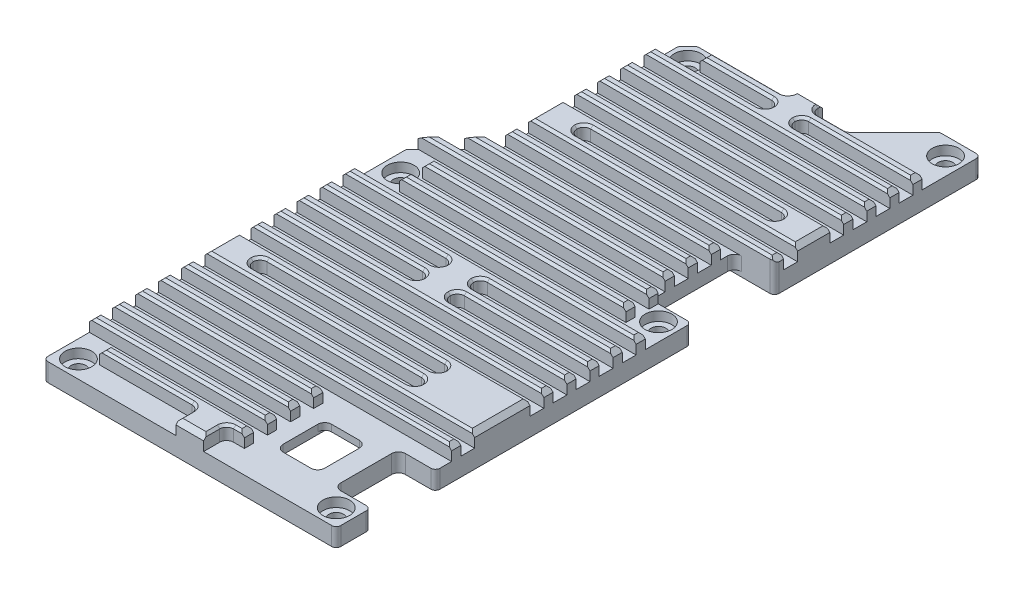
SolidWorks part; units mm, degrees
ref_plane "Front Plane" through (0, 0, 0) normal (0, 0, 1) x (1, 0, 0)
ref_plane "Top Plane" through (0, 0, 0) normal (0, 1, 0) x (1, 0, 0)
ref_plane "Right Plane" through (0, 0, 0) normal (1, 0, 0) x (0, 0, -1)
sketch "Sketch1" plane through (0, 0, 0) normal (0, 1, 0) x (1, 0, 0)
  line L2 (0, 1) -> (0, 78.3258)
  line L15 (63.5, 138.7) -> (63.5, 96)
  line L19 (10.16, 89.5213) -> (10.16, 127.0958)
  line L24 (0.2929, 79.0329) -> (9.7207, 88.4607)
  line L25 (10.4529, 127.8029) -> (11.8971, 129.2471)
  line L26 (1, 0) -> (62.5, 0)
  line L27 (12.6042, 129.54) -> (43.8287, 129.54)
  line L28 (62.5, 139.7) -> (55.0242, 139.7)
  line L29 (54.3171, 139.4071) -> (44.8893, 129.9793)
  line L30 (63.5, 76) -> (63.5, 22.5)
  line L31 (56.3, 95) -> (62.5, 95)
  line L32 (54.8, 93.5) -> (54.8, 78.5)
  line L33 (56.3, 77) -> (62.5, 77)
  line L35 (63.5, 6.5) -> (63.5, 1)
  line L36 (57, 21.5) -> (62.5, 21.5)
  line L37 (55.5, 20) -> (55.5, 9)
  line L38 (57, 7.5) -> (62.5, 7.5)
  arc A0 (63.5, 138.7) -> (62.5, 139.7) centre (62.5, 138.7) ccw
  arc A1 (54.3171, 139.4071) -> (55.0242, 139.7) centre (55.0242, 138.7) cw
  arc A2 (11.8971, 129.2471) -> (12.6042, 129.54) centre (12.6042, 128.54) cw
  arc A3 (10.4529, 127.8029) -> (10.16, 127.0958) centre (11.16, 127.0958) ccw
  arc A4 (0, 78.3258) -> (0.2929, 79.0329) centre (1, 78.3258) cw
  arc A5 (62.5, 0) -> (63.5, 1) centre (62.5, 1) ccw
  arc A6 (1, 0) -> (0, 1) centre (1, 1) cw
  arc A7 (43.8287, 129.54) -> (44.8893, 129.9793) centre (43.8287, 131.04) ccw
  arc A8 (9.7207, 88.4607) -> (10.16, 89.5213) centre (8.66, 89.5213) ccw
  arc A9 (54.8, 78.5) -> (56.3, 77) centre (56.3, 78.5) ccw
  arc A10 (56.3, 95) -> (54.8, 93.5) centre (56.3, 93.5) ccw
  arc A11 (62.5, 77) -> (63.5, 76) centre (62.5, 76) cw
  arc A12 (62.5, 95) -> (63.5, 96) centre (62.5, 96) ccw
  arc A13 (62.5, 7.5) -> (63.5, 6.5) centre (62.5, 6.5) cw
  arc A14 (62.5, 21.5) -> (63.5, 22.5) centre (62.5, 22.5) ccw
  arc A15 (55.5, 9) -> (57, 7.5) centre (57, 9) ccw
  arc A16 (57, 21.5) -> (55.5, 20) centre (57, 20) ccw
  point P15 (12.19, 129.54)
  point P20 (0, 78.74)
  point P27 (44.45, 129.54)
  point P40 (63.5, 77)
  point P49 (63.5, 7.5)
  dimension "D6" = 12.19
  dimension "D7" = 135
  dimension "D8" = 19.05
  dimension "D9" = 135
  dimension "D10" = 135
  dimension "D4" = 78.74
  dimension "D5" = 10.16
  dimension "D18" = 1
  dimension "D19" = 1
  dimension "D12" = 1
  dimension "D13" = 1.5
  dimension "D17" = 1.5
  dimension "D20" = 1.5
  dimension "D2" = 10.16
  dimension "D3" = 63.5
  dimension "D11" = 139.7
  dimension "D14" = 8.7
  dimension "D15" = 18
  dimension "D16" = 77
  dimension "D21" = 8
  dimension "D22" = 14
  dimension "D23" = 7.5
extrude "Boss-Extrude1" add sketch "Sketch1" along normal blind 6.95
sketch "Sketch2" plane through (0, 0, 0) normal (0, 1, 0) x (1, 0, 0)
  line L514 (62.5, 95) -> (46.76, 95)
  line L515 (56.3, 95) -> (62.5, 95) construction
  line L516 (45.26, 96.5) -> (45.26, 107.75)
  line L517 (43.76, 109.25) -> (39.26, 109.25)
  line L518 (37.76, 107.75) -> (37.76, 94)
  line L519 (62.5, 95) -> (62.5, 77)
  line L520 (34.76, 91) -> (34.76, 71.5)
  line L521 (36.26, 70) -> (53.76, 70)
  line L522 (55.26, 71.5) -> (55.26, 75.5)
  line L523 (62.5, 77) -> (56.76, 77)
  line L524 (63.5, 22.5) -> (63.5, 76) construction
  line L525 (34.76, 91) -> (36.26, 91) construction
  line L526 (36.26, 91) -> (36.26, 92.5) construction
  line L527 (36.26, 92.5) -> (36.26, 94) construction
  line L528 (36.26, 94) -> (37.76, 94) construction
  line L529 (19.51, 122.65) -> (56.01, 122.65)
  line L530 (57.51, 121.15) -> (57.51, 109.65)
  line L531 (56.01, 108.15) -> (49.51, 108.15)
  line L532 (48.01, 109.65) -> (48.01, 111.4)
  line L533 (46.26, 113.15) -> (33.01, 113.15)
  line L534 (31.51, 111.65) -> (31.51, 99.65)
  line L535 (30.01, 98.15) -> (19.51, 98.15)
  line L536 (18.01, 99.65) -> (18.01, 121.15)
  line L1015 (23.76, 42.1) -> (28.76, 42.1)
  line L1016 (21.76, 40.1) -> (21.76, 29.35)
  line L1017 (23.76, 27.35) -> (28.76, 27.35)
  line L1018 (30.76, 40.1) -> (30.76, 29.35)
  arc A13 (62.5, 95) -> (63.5, 96) centre (62.5, 96) ccw construction
  arc A14 (36.26, 92.5) -> (34.76, 91) centre (36.26, 91) ccw
  arc A15 (36.26, 92.5) -> (37.76, 94) centre (36.26, 94) ccw
  arc A16 (34.76, 71.5) -> (36.26, 70) centre (36.26, 71.5) ccw
  arc A17 (53.76, 70) -> (55.26, 71.5) centre (53.76, 71.5) ccw
  arc A18 (55.26, 75.5) -> (56.76, 77) centre (56.76, 75.5) cw
  arc A19 (46.76, 95) -> (45.26, 96.5) centre (46.76, 96.5) cw
  arc A20 (45.26, 107.75) -> (43.76, 109.25) centre (43.76, 107.75) ccw
  arc A21 (39.26, 109.25) -> (37.76, 107.75) centre (39.26, 107.75) ccw
  arc A22 (31.51, 99.65) -> (30.01, 98.15) centre (30.01, 99.65) cw
  arc A23 (19.51, 98.15) -> (18.01, 99.65) centre (19.51, 99.65) cw
  arc A24 (19.51, 122.65) -> (18.01, 121.15) centre (19.51, 121.15) ccw
  arc A25 (56.01, 122.65) -> (57.51, 121.15) centre (56.01, 121.15) cw
  arc A26 (57.51, 109.65) -> (56.01, 108.15) centre (56.01, 109.65) cw
  arc A27 (49.51, 108.15) -> (48.01, 109.65) centre (49.51, 109.65) cw
  arc A29 (33.01, 113.15) -> (31.51, 111.65) centre (33.01, 111.65) ccw
  arc A49 (46.26, 113.15) -> (48.01, 111.4) centre (46.26, 111.4) cw
  arc A63 (28.76, 27.35) -> (30.76, 29.35) centre (28.76, 29.35) ccw
  arc A64 (23.76, 27.35) -> (21.76, 29.35) centre (23.76, 29.35) cw
  arc A65 (28.76, 42.1) -> (30.76, 40.1) centre (28.76, 40.1) cw
  arc A66 (23.76, 42.1) -> (21.76, 40.1) centre (23.76, 40.1) ccw
  point P603 (26.26, 27.35)
  dimension "D15" = 1.5
  dimension "D26" = 1.5
  dimension "D50" = 1.75
  dimension "D51" = 1.5
  dimension "D10" = 2
  dimension "D2" = 28.74
  dimension "D3" = 14.75
  dimension "D4" = 18.24
  dimension "D6" = 7.5
  dimension "D7" = 9
  dimension "D8" = 39.25
  dimension "D9" = 7
  dimension "D11" = 27.9
  dimension "D12" = 22.5
  dimension "D13" = 4
  dimension "D14" = 20.5
  dimension "D16" = 39.5
  dimension "D17" = 13.5
  dimension "D18" = 9.5
  dimension "D19" = 9.5
  dimension "D20" = 14.5
  dimension "D21" = 24.5
  dimension "D23" = 3.9
  dimension "D25" = 2.75
sketch "Sketch11" plane through (0, 0, 0) normal (0, 1, 0) x (1, 0, 0)
  line L0 (31.2328, 67.2228) -> (31.76, 67.75) construction
  line L1 (31.76, 68.4956) -> (31.76, 67.75) construction
  line L11 (3.01, 47.7456) -> (3.01, 47) construction
  line L12 (3.5372, 46.4728) -> (3.01, 47) construction
  line L13 (27.7328, 52.2228) -> (28.26, 52.75) construction
  line L14 (28.26, 53.4956) -> (28.26, 52.75) construction
  line L23 (18.76, 92.25) -> (30.26, 92.25)
  line L24 (31.76, 90.75) -> (31.76, 68.4956)
  line L25 (31.2328, 67.2228) -> (28.7872, 64.7772)
  line L26 (28.26, 63.5044) -> (28.26, 53.4956)
  line L27 (27.7328, 52.2228) -> (20.5372, 45.0272)
  line L28 (20.01, 43.7544) -> (20.01, 26)
  line L29 (21.51, 24.5) -> (49.76, 24.5)
  line L30 (51.26, 23) -> (51.26, 6)
  line L31 (49.76, 4.5) -> (43.26, 4.5)
  line L32 (41.76, 6) -> (41.76, 6.74)
  line L33 (41, 7.5) -> (19.5056, 7.5)
  line L34 (18.2328, 8.0272) -> (9.7872, 16.4728)
  line L35 (9.26, 17.7456) -> (9.26, 40.0044)
  line L36 (8.7328, 41.2772) -> (3.5372, 46.4728)
  line L37 (3.01, 47.7456) -> (3.01, 67.5)
  line L38 (4.51, 69) -> (15.76, 69)
  line L39 (17.26, 70.5) -> (17.26, 90.75)
  line L40 (9.26, 17.7456) -> (9.26, 17) construction
  line L41 (9.7872, 16.4728) -> (9.26, 17) construction
  line L42 (1, 0) -> (62.5, 0) construction
  line L43 (63.5, 1) -> (63.5, 6.5) construction
  arc A15 (43.26, 4.5) -> (41.76, 6) centre (43.26, 6) cw
  arc A16 (51.26, 6) -> (49.76, 4.5) centre (49.76, 6) cw
  arc A17 (49.76, 24.5) -> (51.26, 23) centre (49.76, 23) cw
  arc A18 (20.01, 26) -> (21.51, 24.5) centre (21.51, 26) ccw
  arc A19 (30.26, 92.25) -> (31.76, 90.75) centre (30.26, 90.75) cw
  arc A20 (18.76, 92.25) -> (17.26, 90.75) centre (18.76, 90.75) ccw
  arc A21 (15.76, 69) -> (17.26, 70.5) centre (15.76, 70.5) ccw
  arc A22 (3.01, 67.5) -> (4.51, 69) centre (4.51, 67.5) cw
  arc A23 (19.5056, 7.5) -> (18.2328, 8.0272) centre (19.5056, 9.3) cw
  arc A24 (9.7872, 16.4728) -> (9.26, 17.7456) centre (11.06, 17.7456) cw
  arc A25 (31.76, 68.4956) -> (31.2328, 67.2228) centre (29.96, 68.4956) cw
  arc A26 (28.7872, 64.7772) -> (28.26, 63.5044) centre (30.06, 63.5044) ccw
  arc A27 (28.26, 53.4956) -> (27.7328, 52.2228) centre (26.46, 53.4956) cw
  arc A28 (20.5372, 45.0272) -> (20.01, 43.7544) centre (21.81, 43.7544) ccw
  arc A29 (9.26, 40.0044) -> (8.7328, 41.2772) centre (7.46, 40.0044) ccw
  arc A30 (3.5372, 46.4728) -> (3.01, 47.7456) centre (4.81, 47.7456) cw
  arc A31 (41.76, 6.74) -> (41, 7.5) centre (41, 6.74) ccw
  dimension "D6" = 16.25
  dimension "D30" = 1.5
  dimension "D31" = 1.8
  dimension "D32" = 0.76
  dimension "D4" = 24.5
  dimension "D5" = 22
  dimension "D7" = 7.5
  dimension "D8" = 9.26
  dimension "D16" = 14.5
  dimension "D17" = 23.25
  dimension "D19" = 14.25
  dimension "D21" = 135
  dimension "D22" = 3.5
  dimension "D23" = 6.25
  dimension "D24" = 10.75
  dimension "D25" = 17
  dimension "D26" = 67.75
  dimension "D27" = 42
  dimension "D28" = 20
  dimension "D29" = 9.5
  dimension "D35" = 52
extrude "Cut-Extrude4" cut sketch "Sketch2" along normal blind 1 contours L533 A49 L532 A27 L531 A26 L530 A25 L529 A24 L536 A23 L535 A22 L534 A29 | L517 A21 L518 A15 A14 L520 A16 L521 A17 L522 A18 L523 L519 L514 A19 L516 A20 | A66 L1015 A65 L1018 A63 L1017 A64 L1016
extrude "Cut-Extrude5" cut sketch "Sketch11" along normal blind 2
sketch "Sketch12" plane through (0, 0, 0) normal (0, -1, 0) x (1, 0, 0)
  line L0 (62.5, -77) -> (56.3, -77) construction
  line L1 (54.8, -42.1) -> (34.55, -42.1)
  line L2 (56.8, -40.1) -> (56.8, -29.35)
  line L3 (54.8, -27.35) -> (34.55, -27.35)
  line L4 (32.55, -40.1) -> (32.55, -29.35)
  line L5 (54.8, -78.5) -> (54.8, -93.5) construction
  arc A0 (54.8, -42.1) -> (56.8, -40.1) centre (54.8, -40.1) ccw
  arc A1 (56.8, -29.35) -> (54.8, -27.35) centre (54.8, -29.35) ccw
  arc A2 (34.55, -27.35) -> (32.55, -29.35) centre (34.55, -29.35) ccw
  arc A3 (34.55, -42.1) -> (32.55, -40.1) centre (34.55, -40.1) cw
  dimension "D5" = 2
  dimension "D1" = 14.75
  dimension "D2" = 24.25
  dimension "D3" = 34.9
  dimension "D4" = 2
extrude "Cut-Extrude6" cut sketch "Sketch12" against normal blind 1.2
sketch "Sketch13" plane through (0, 0, 0) normal (0, -1, 0) x (1, 0, 0)
  line L0 (36.8, -67) -> (55.3, -67)
  line L1 (56.8, -65.5) -> (56.8, -46.5)
  line L2 (55.3, -45) -> (34.05, -45)
  line L3 (32.55, -46.5) -> (32.55, -50)
  line L4 (34.05, -51.5) -> (34.5, -51.5)
  line L5 (35.3, -52.3) -> (35.3, -65.5)
  line L6 (62.5, -77) -> (56.3, -77) construction
  line L7 (54.8, -78.5) -> (54.8, -93.5) construction
  arc A0 (32.55, -50) -> (34.05, -51.5) centre (34.05, -50) ccw
  arc A1 (34.05, -45) -> (32.55, -46.5) centre (34.05, -46.5) ccw
  arc A2 (36.8, -67) -> (35.3, -65.5) centre (36.8, -65.5) cw
  arc A3 (56.8, -46.5) -> (55.3, -45) centre (55.3, -46.5) ccw
  arc A4 (55.3, -67) -> (56.8, -65.5) centre (55.3, -65.5) ccw
  arc A5 (34.5, -51.5) -> (35.3, -52.3) centre (34.5, -52.3) cw
  dimension "D7" = 1.5
  dimension "D8" = 0.8
  dimension "D1" = 24.25
  dimension "D2" = 22
  dimension "D3" = 21.5
  dimension "D4" = 6.5
  dimension "D5" = 10
  dimension "D6" = 2
extrude "Cut-Extrude7" cut sketch "Sketch13" against normal blind 2
sketch "Sketch14" plane through (0, 6.95, 0) normal (0, 1, 0) x (1, 0, 0)
  line L1 (43.5, 19) -> (49.5, 19)
  line L2 (42, 17.5) -> (42, 10)
  line L3 (43.5, 8.5) -> (49.5, 8.5)
  line L4 (51, 17.5) -> (51, 10)
  line L5 (57, 21.5) -> (62.5, 21.5) construction
  line L6 (63.5, 22.5) -> (63.5, 76) construction
  arc A0 (49.5, 8.5) -> (51, 10) centre (49.5, 10) ccw
  arc A1 (42, 10) -> (43.5, 8.5) centre (43.5, 10) ccw
  arc A2 (49.5, 19) -> (51, 17.5) centre (49.5, 17.5) cw
  arc A3 (43.5, 19) -> (42, 17.5) centre (43.5, 17.5) ccw
  dimension "D5" = 1.5
  dimension "D1" = 9
  dimension "D2" = 10.5
  dimension "D3" = 12.5
  dimension "D4" = 2.5
extrude "Cut-Extrude8" cut sketch "Sketch14" against normal through all
sketch "Sketch15" plane through (0, 6.95, 0) normal (0, 1, 0) x (1, 0, 0)
  line L0 (0, 78.3258) -> (0, 1) construction
  line L1 (0, 5) -> (63.5, 5)
  line L2 (0, 5) -> (0, 2)
  line L3 (0, 2) -> (63.5, 2)
  line L4 (63.5, 5) -> (63.5, 2)
  line L5 (63.5, 1) -> (63.5, 6.5) construction
  line L6 (1, 0) -> (62.5, 0) construction
  dimension "D1" = 2
  dimension "D2" = 3
extrude "Cut-Extrude9" cut sketch "Sketch15" against normal blind 3
pattern_linear "LPattern1" count 28 spacing 5 along (0, 0, -1) of "Cut-Extrude9"
sketch "Sketch16" plane through (0, 6.95, 0) normal (0, 1, 0) x (1, 0, 0)
  line L0 (63.5, 2) -> (63.5, 5) construction
  line L2 (38.6, 22) -> (38.6, 2)
  line L4 (63.5, 20) -> (63.5, 0)
  line L7 (43.8287, 129.54) -> (12.6042, 129.54) construction
  line L8 (43.8287, 129.54) -> (63.5, 129.54)
  line L9 (43.8287, 129.54) -> (43.8287, 139.7)
  line L10 (43.8287, 139.7) -> (63.5, 139.7)
  line L11 (63.5, 129.54) -> (63.5, 139.7)
  line L12 (63.5, 132) -> (63.5, 135) construction
  line L13 (62.5, 139.7) -> (55.0242, 139.7) construction
  line L14 (0, 2) -> (63.5, 2) construction
  line L15 (0, 10) -> (7.2, 10)
  line L16 (0, 10) -> (0, 0)
  line L18 (7.2, 10) -> (7.2, 2)
  line L21 (7.2, 2) -> (38.6, 2)
  line L23 (42, 10) -> (0, 10) construction
  line L24 (0, 0) -> (63.5, 0)
  line L25 (0, 10) -> (0, 7) construction
  line L26 (1, 0) -> (62.5, 0) construction
  line L27 (62.5, 77) -> (0, 77) construction
  line L28 (56.3, 77) -> (63.5, 77)
  line L29 (56.3, 77) -> (56.3, 70)
  line L30 (56.3, 70) -> (63.5, 70)
  line L31 (63.5, 77) -> (63.5, 70)
  line L32 (63.5, 70) -> (0, 70) construction
  line L33 (63.5, 67) -> (63.5, 70) construction
  line L34 (63.5, 70) -> (0, 70) construction
  line L35 (0, 77) -> (7.2, 77)
  line L36 (0, 77) -> (0, 70)
  line L37 (0, 70) -> (7.2, 70)
  line L38 (7.2, 77) -> (7.2, 70)
  line L39 (0, 22) -> (63.366, 22) construction
  line L40 (10.16, 122) -> (17.36, 122)
  line L41 (10.16, 122) -> (10.16, 129.54)
  line L42 (10.16, 129.54) -> (17.36, 129.54)
  line L43 (17.36, 122) -> (17.36, 129.54)
  line L46 (38.6, 22) -> (63.5, 22)
  line L47 (63.5, 20) -> (63.5, 22)
  line L49 (0, 22) -> (63.366, 22) construction
  dimension "D1" = 24.9
  dimension "D2" = 7.2
  dimension "D3" = 7.2
  dimension "D4" = 7.2
  dimension "D5" = 7.2
extrude "Cut-Extrude10" cut sketch "Sketch16" against normal blind 3
hole_wizard "Ø3.2 (3.2) Diameter Hole1" positions "Sketch18" profile "Sketch17" hole size "Ø3.2" standard "ISO" end condition up to next
sketch "Sketch18" plane through (0, 3.95, 0) normal (0, 1, 0) x (1, 0, 0)
  line L0 (1, 0) -> (62.5, 0) construction
  line L1 (63.5, 1) -> (63.5, 6.5) construction
  line L2 (0, 10) -> (0, 1) construction
  line L3 (63.5, 67) -> (63.5, 76) construction
  line L4 (0, 78.3258) -> (0, 67) construction
  line L5 (10.16, 127.0958) -> (10.16, 122) construction
  line L6 (43.8287, 129.54) -> (12.6042, 129.54) construction
  line L7 (63.5, 127) -> (63.5, 138.7) construction
  line L8 (62.5, 139.7) -> (55.0242, 139.7) construction
  point P0 (59.69, 3.81)
  point P1 (3.81, 3.81)
  point P3 (3.81, 73.66)
  point P5 (59.69, 73.66)
  point P7 (13.97, 125.73)
  point P9 (59.69, 135.89)
  dimension "D1" = 3.81
  dimension "D2" = 3.81
  dimension "D3" = 3.81
  dimension "D4" = 3.81
  dimension "D5" = 3.81
  dimension "D6" = 3.81
  dimension "D7" = 3.81
  dimension "D8" = 3.81
  dimension "D9" = 3.81
  dimension "D10" = 3.81
  dimension "D11" = 69.85
  dimension "D12" = 69.85
sketch "Sketch17" plane through (59.69, 3.95, -3.81) normal (1, 0, 0) x (0, 0, 1)
  line L0 (0, 0) -> (0, 3.95)
  line L1 (0, 3.95) -> (1.6, 3.95)
  line L2 (1.6, 3.95) -> (1.6, 0)
  line L5 (1.6, 0) -> (0, 0)
  line L11 (0, -6.35) -> (0, 107.95) construction
  dimension "Thru Hole Dia." = 3.2
  dimension "Thru Hole Depth" = 3.95
sketch "Sketch19" plane through (0, 3.95, 0) normal (0, 1, 0) x (1, 0, 0)
  circle A0 centre (3.81, 3.81) radius 2.9
  circle A1 centre (59.69, 3.81) radius 2.9
  circle A2 centre (3.81, 73.66) radius 2.9
  circle A3 centre (59.69, 73.66) radius 2.9
  circle A4 centre (13.97, 125.73) radius 2.9
  circle A5 centre (59.69, 135.89) radius 2.9
  dimension "D1" = 5.8
  dimension "D2" = 5.8
  dimension "D3" = 5.8
  dimension "D4" = 5.8
  dimension "D5" = 5.8
  dimension "D6" = 5.8
extrude "Cut-Extrude11" cut sketch "Sketch19" against normal blind 2
sketch "Sketch20" plane through (0, 3.95, 0) normal (0, 1, 0) x (1, 0, 0)
  line L0 (1, 0) -> (62.5, 0) construction
  line L1 (28.75, 0) -> (34.75, 0)
  line L2 (28.75, 0) -> (28.75, 7)
  line L3 (28.75, 7) -> (34.75, 7)
  line L4 (34.75, 0) -> (34.75, 7)
  line L5 (63.5, 30) -> (0, 30) construction
  line L7 (43.8287, 129.54) -> (12.6042, 129.54) construction
  line L8 (34.41, 129.54) -> (39.41, 129.54)
  line L9 (34.41, 129.54) -> (34.41, 122)
  line L10 (34.41, 122) -> (39.41, 122)
  line L11 (39.41, 129.54) -> (39.41, 122)
  line L12 (63.5, 35) -> (0, 35) construction
  line L13 (10.16, 127.0958) -> (10.16, 122) construction
  line L14 (10.16, 122) -> (63.5, 122) construction
  line L15 (0, 42) -> (7, 42)
  line L16 (0, 42) -> (0, 35)
  line L17 (0, 35) -> (7, 35)
  line L18 (7, 42) -> (7, 35)
  line L19 (31.75, 7) -> (31.75, 0) construction
  line L20 (63.5, 42) -> (48.5, 42)
  line L21 (63.5, 42) -> (63.5, 30)
  line L22 (63.5, 30) -> (48.5, 30)
  line L23 (48.5, 42) -> (48.5, 30)
  line L24 (0, 10) -> (0, 1) construction
  line L25 (28.75, 60) -> (34.75, 60)
  line L26 (28.75, 60) -> (28.75, 52)
  line L27 (28.75, 52) -> (34.75, 52)
  line L28 (34.75, 60) -> (34.75, 52)
  line L30 (0, 55) -> (0, 52) construction
  line L35 (63.5, 60) -> (0, 60) construction
  line L36 (0, 52) -> (63.5, 52) construction
  line L37 (10.16, 95) -> (62.5, 95) construction
  line L38 (10.16, 102) -> (17.16, 102)
  line L39 (10.16, 102) -> (10.16, 95)
  line L40 (10.16, 95) -> (17.16, 95)
  line L41 (17.16, 102) -> (17.16, 95)
  line L42 (63.5, 100) -> (10.16, 100) construction
  line L43 (56.5, 100) -> (63.5, 100)
  line L44 (56.5, 100) -> (56.5, 107)
  line L45 (56.5, 107) -> (63.5, 107)
  line L46 (63.5, 100) -> (63.5, 107)
  line L47 (7.2, 7) -> (38.6, 7) construction
  point P20 (34.41, 125.77)
  point P47 (28.75, 56)
  point P60 (63.5, 103.5)
  dimension "D2" = 6
  dimension "D3" = 5
  dimension "D4" = 24.25
  dimension "D5" = 7
  dimension "D6" = 15
  dimension "D7" = 6
  dimension "D8" = 28.75
  dimension "D9" = 7
  dimension "D10" = 7
  dimension "D11" = 31.75
extrude "Boss-Extrude2" add sketch "Sketch20" along normal up to surface (3 mm away) up to face at (22.9, 6.95, -6)
fillet "Fillet1" radius 1.5 26 edges at (39.41, 5.45, -122) (39.41, 5.45, -125) (39.41, 5.45, -127) (34.41, 5.45, -127) (34.41, 5.45, -122) (34.41, 5.45, -125) (56.5, 5.45, -102) (56.5, 5.45, -105) (17.16, 5.45, -97) (17.16, 5.45, -100) (28.75, 5.45, -52) (28.75, 5.45, -55) (28.75, 5.45, -57) (28.75, 5.45, -60) (34.75, 5.45, -60) (34.75, 5.45, -57) (34.75, 5.45, -52) (34.75, 5.45, -55) (7, 5.45, -37) (7, 5.45, -40) (34.75, 5.45, -5) (28.75, 5.45, -5) (48.5, 5.45, -37) (48.5, 5.45, -40) (48.5, 5.45, -32) (48.5, 5.45, -35)
sketch "Sketch21" plane through (0, 0, 0) normal (0, -1, 0) x (1, 0, 0)
  line L0 (45.26, -96.5) -> (45.26, -107.75) construction
  line L1 (43.76, -109.25) -> (39.26, -109.25)
  line L2 (45.26, -107.75) -> (45.26, -94)
  line L3 (43.76, -92.5) -> (39.26, -92.5)
  line L4 (37.76, -107.75) -> (37.76, -94)
  line L5 (37.76, -107.75) -> (37.76, -94) construction
  line L6 (43.76, -109.25) -> (39.26, -109.25) construction
  line L7 (36.26, -70) -> (53.76, -70) construction
  line L8 (53.76, -77.5) -> (42.76, -77.5)
  line L9 (55.26, -76) -> (55.26, -71.5)
  line L10 (53.76, -70) -> (42.76, -70)
  line L11 (41.26, -76) -> (41.26, -71.5)
  line L12 (55.26, -71.5) -> (55.26, -75.5) construction
  line L13 (62.5, -77) -> (56.76, -77) construction
  arc A0 (39.26, -92.5) -> (37.76, -94) centre (39.26, -94) ccw
  arc A1 (45.26, -94) -> (43.76, -92.5) centre (43.76, -94) ccw
  arc A2 (39.26, -109.25) -> (37.76, -107.75) centre (39.26, -107.75) cw
  arc A3 (43.76, -109.25) -> (45.26, -107.75) centre (43.76, -107.75) ccw
  arc A4 (42.76, -77.5) -> (41.26, -76) centre (42.76, -76) cw
  arc A5 (42.76, -70) -> (41.26, -71.5) centre (42.76, -71.5) ccw
  arc A6 (55.26, -71.5) -> (53.76, -70) centre (53.76, -71.5) ccw
  arc A7 (53.76, -77.5) -> (55.26, -76) centre (53.76, -76) ccw
  point P33 (41.26, -70)
  dimension "D1" = 1.5
  dimension "D4" = 1.5
  dimension "D2" = 0.5
  dimension "D3" = 14
extrude "Cut-Extrude12" cut sketch "Sketch21" against normal blind 3 contours L9 A6 L10 A5 L11 A4 L8 A7 | A3 L1 A2 L4 A0 L3 A1 L2
sketch "Sketch22" plane through (0, 0, 0) normal (0, -1, 0) x (1, 0, 0)
  line L0 (51.26, -6) -> (51.26, -23) construction
  line L1 (49.76, -24.5) -> (43.5, -24.5)
  line L2 (51.26, -23) -> (51.26, -18.344)
  line L4 (42, -23) -> (42, -16.844)
  line L5 (49.76, -24.5) -> (21.51, -24.5) construction
  line L6 (42, -10) -> (42, -17.5) construction
  line L8 (49.76, -16.844) -> (42, -16.844)
  line L16 (37.55, -35.45) -> (34.05, -35.45)
  line L17 (39.05, -33.95) -> (39.05, -30.95)
  line L18 (37.55, -29.45) -> (34.05, -29.45)
  line L19 (32.55, -33.95) -> (32.55, -30.95)
  line L20 (32.55, -29.35) -> (32.55, -40.1) construction
  line L21 (54.8, -27.35) -> (34.55, -27.35) construction
  arc A0 (43.5, -24.5) -> (42, -23) centre (43.5, -23) cw
  arc A3 (49.76, -24.5) -> (51.26, -23) centre (49.76, -23) ccw
  arc A4 (51.26, -18.344) -> (49.76, -16.844) centre (49.76, -18.344) ccw
  arc A9 (34.05, -29.45) -> (32.55, -30.95) centre (34.05, -30.95) ccw
  arc A10 (39.05, -30.95) -> (37.55, -29.45) centre (37.55, -30.95) ccw
  arc A11 (34.05, -35.45) -> (32.55, -33.95) centre (34.05, -33.95) cw
  arc A12 (37.55, -35.45) -> (39.05, -33.95) centre (37.55, -33.95) ccw
  dimension "D1" = 1.5
  dimension "D2" = 1.5
  dimension "D3" = 1.5
  dimension "D5" = 1.5
  dimension "D6" = 6
  dimension "D7" = 6.5
  dimension "D8" = 2.1
extrude "Cut-Extrude13" cut sketch "Sketch22" against normal blind 2.5
sketch "Sketch25" plane through (0, 0, 0) normal (0, -1, 0) x (1, 0, 0)
  line L0 (19.51, -122.65) -> (56.01, -122.65) construction
  line L1 (30.01, -122.65) -> (19.51, -122.65)
  line L2 (31.51, -121.15) -> (31.51, -99.65)
  line L3 (30.01, -98.15) -> (19.51, -98.15)
  line L4 (18.01, -121.15) -> (18.01, -99.65)
  line L5 (30.01, -98.15) -> (19.51, -98.15) construction
  line L6 (18.01, -99.65) -> (18.01, -121.15) construction
  line L7 (31.51, -111.65) -> (31.51, -99.65) construction
  line L8 (15.76, -69) -> (4.51, -69) construction
  line L9 (10.71, -57.3) -> (7.71, -57.3)
  line L10 (12.21, -55.8) -> (12.21, -52.8)
  line L11 (10.71, -51.3) -> (7.71, -51.3)
  line L12 (6.21, -55.8) -> (6.21, -52.8)
  line L13 (3.01, -67.5) -> (3.01, -47.7456) construction
  arc A0 (30.01, -122.65) -> (31.51, -121.15) centre (30.01, -121.15) ccw
  arc A1 (31.51, -99.65) -> (30.01, -98.15) centre (30.01, -99.65) ccw
  arc A2 (19.51, -98.15) -> (18.01, -99.65) centre (19.51, -99.65) ccw
  arc A3 (19.51, -122.65) -> (18.01, -121.15) centre (19.51, -121.15) cw
  arc A4 (7.71, -51.3) -> (6.21, -52.8) centre (7.71, -52.8) ccw
  arc A5 (12.21, -52.8) -> (10.71, -51.3) centre (10.71, -52.8) ccw
  arc A6 (7.71, -57.3) -> (6.21, -55.8) centre (7.71, -55.8) cw
  arc A7 (10.71, -57.3) -> (12.21, -55.8) centre (10.71, -55.8) ccw
  dimension "D1" = 1.5
  dimension "D2" = 1.5
  dimension "D3" = 6
  dimension "D4" = 6
  dimension "D5" = 11.7
  dimension "D6" = 3.2
extrude "Cut-Extrude14" cut sketch "Sketch25" against normal blind 2.5
sketch "Sketch26" plane through (0, 0, 0) normal (0, -1, 0) x (1, 0, 0)
  line L0 (55.3, -37.65) -> (52.2, -37.65)
  line L1 (56.8, -36.15) -> (56.8, -33.15)
  line L2 (55.3, -31.65) -> (52.2, -31.65)
  line L3 (50.7, -36.15) -> (50.7, -33.15)
  line L4 (56.8, -40.1) -> (56.8, -29.35) construction
  line L5 (54.8, -27.35) -> (34.55, -27.35) construction
  arc A0 (55.3, -37.65) -> (56.8, -36.15) centre (55.3, -36.15) ccw
  arc A1 (56.8, -33.15) -> (55.3, -31.65) centre (55.3, -33.15) ccw
  arc A2 (52.2, -31.65) -> (50.7, -33.15) centre (52.2, -33.15) ccw
  arc A3 (52.2, -37.65) -> (50.7, -36.15) centre (52.2, -36.15) cw
  arc A4 (55.3, -31.65) -> (56.8, -33.15) centre (55.3, -33.15) cw
  point P6 (58.2695, -36.9223)
  dimension "D1" = 1.5
  dimension "D2" = 1.5
  dimension "D3" = 6
  dimension "D4" = 6.1
  dimension "D5" = 4.3
extrude "Cut-Extrude15" cut sketch "Sketch26" against normal blind 3.5 contours A3 L0 A0 L1 A1 L2 A2 L3
sketch "Sketch27" plane through (0, 2, 0) normal (0, -1, 0) x (1, 0, 0)
  line L0 (19.5056, -7.5) -> (41, -7.5) construction
  line L1 (34.86, -17.2) -> (29.86, -17.2)
  line L2 (35.36, -16.7) -> (35.36, -11.7)
  line L3 (34.86, -11.2) -> (29.86, -11.2)
  line L4 (29.36, -16.7) -> (29.36, -11.7)
  line L5 (51.26, -6) -> (51.26, -23) construction
  arc A0 (29.86, -11.2) -> (29.36, -11.7) centre (29.86, -11.7) ccw
  arc A1 (35.36, -11.7) -> (34.86, -11.2) centre (34.86, -11.7) ccw
  arc A2 (29.86, -17.2) -> (29.36, -16.7) centre (29.86, -16.7) cw
  arc A3 (34.86, -17.2) -> (35.36, -16.7) centre (34.86, -16.7) ccw
  dimension "D1" = 0.5
  dimension "D2" = 6
  dimension "D3" = 6
  dimension "D4" = 3.7
  dimension "D5" = 15.9
extrude "Boss-Extrude3" add sketch "Sketch27" along normal blind 0.5
chamfer "Chamfer1" distance 0.5 angle 45 90 edges at (34.41, 6.95, -129.02) (33.9707, 6.95, -127.4393) (25.135, 6.95, -127) (39.41, 6.95, -129.02) (39.8493, 6.95, -127.4393) (52.205, 6.95, -127) (52.205, 6.95, -125) (39.8493, 6.95, -124.5607) (39.8493, 6.95, -122.4393) (52.205, 6.95, -122) (25.135, 6.95, -125) (33.9707, 6.95, -124.5607) (33.9707, 6.95, -122.4393) (21.535, 6.95, -122) (36.83, 6.95, -120) (36.83, 6.95, -117) (36.83, 6.95, -115) (36.83, 6.95, -112) (36.83, 6.95, -110) (36.83, 6.95, -107) (32.58, 6.95, -105) (56.0607, 6.95, -104.5607) (56.0607, 6.95, -102.4393) (32.58, 6.95, -102) (41.08, 6.95, -100) (17.5993, 6.95, -99.5607) (17.5993, 6.95, -97.4393) (41.08, 6.95, -97) (63.5, 6.95, -96.5) (63.2071, 6.95, -95.2929) (36.33, 6.95, -95) (32.48, 6.95, -92) (32.48, 6.95, -90) (31.53, 6.95, -87) (30.53, 6.95, -85) (29.03, 6.95, -82) (28.03, 6.95, -80) (31.75, 6.95, -77) (31.75, 6.95, -75) (49.875, 6.95, -52) (35.1893, 6.95, -52.4393) (35.1893, 6.95, -54.5607) (49.875, 6.95, -55) (49.875, 6.95, -57) (35.1893, 6.95, -57.4393) (35.1893, 6.95, -59.5607) (49.875, 6.95, -60) (31.75, 6.95, -72) (31.75, 6.95, -70) (31.75, 6.95, -67) (31.75, 6.95, -65) (31.75, 6.95, -62) (13.625, 6.95, -57) (28.3107, 6.95, -57.4393) (28.3107, 6.95, -59.5607) (13.625, 6.95, -60) (13.625, 6.95, -55) (28.3107, 6.95, -54.5607) (28.3107, 6.95, -52.4393) (13.625, 6.95, -52) (31.75, 6.95, -50) (31.75, 6.95, -47) (31.75, 6.95, -45) (31.75, 6.95, -42) (27.75, 6.95, -40) (7.4393, 6.95, -39.5607) (48.0607, 6.95, -39.5607) (7.4393, 6.95, -37.4393) (48.0607, 6.95, -37.4393) (27.75, 6.95, -37) (23.5, 6.95, -35) (48.0607, 6.95, -34.5607) (48.0607, 6.95, -32.4393) (23.5, 6.95, -32) (31.75, 6.95, -30) (31.75, 6.95, -27) (31.75, 6.95, -25) (19.3, 6.95, -22) (19.3, 6.95, -20) (19.3, 6.95, -17) (19.3, 6.95, -15) (19.3, 6.95, -12) (19.3, 6.95, -10) (22.9, 6.95, -7) (34.75, 6.95, -1.75) (35.1893, 6.95, -4.5607) (37.425, 6.95, -5) (28.75, 6.95, -1.75) (28.3107, 6.95, -4.5607) (17.225, 6.95, -5)
chamfer "Chamfer2" distance 1 angle 45 46 edges at (38.6, 6.95, -6) (38.6, 6.95, -11) (38.6, 6.95, -16) (38.6, 6.95, -21) (63.5, 6.95, -26) (63.5, 6.95, -36) (63.5, 6.95, -46) (63.5, 6.95, -51) (63.5, 6.95, -56) (63.5, 6.95, -61) (63.5, 6.95, -66) (56.3, 6.95, -71) (56.3, 6.95, -76) (54.8, 6.95, -81) (54.8, 6.95, -86) (54.8, 6.95, -91) (63.5, 6.95, -103.5) (63.5, 6.95, -111) (63.5, 6.95, -116) (63.5, 6.95, -121) (63.5, 6.95, -126) (36.91, 6.95, -129.54) (17.36, 6.95, -126) (10.16, 6.95, -121) (10.16, 6.95, -116) (10.16, 6.95, -111) (10.16, 6.95, -106) (10.16, 6.95, -98.5) (10.16, 6.95, -91) (7.26, 6.95, -86) (2.26, 6.95, -81) (7.2, 6.95, -76) (7.2, 6.95, -71) (0, 6.95, -66) (0, 6.95, -61) (0, 6.95, -56) (0, 6.95, -51) (0, 6.95, -46) (0, 6.95, -38.5) (0, 6.95, -31) (0, 6.95, -26) (31.75, 6.95, 0) (0, 6.95, -21) (0, 6.95, -16) (0, 6.95, -11) (7.2, 6.95, -6)
sketch "Sketch28" plane through (0, 0, -97) normal (0, 0, -1) x (-1, 0, 0)
  line L0 (-63.5, 5.95) -> (-62.5, 6.95)
  line L1 (-63.5, 3.95) -> (-63.5, 6.45) construction
  line L2 (-62.5, 6.95) -> (-40.91, 6.95) construction
  line L3 (-63.5, 5.95) -> (-63.5, 6.95)
  line L4 (-63.5, 6.95) -> (-62.5, 6.95)
  dimension "D1" = 45
  dimension "D2" = 1
extrude "Cut-Extrude16" cut sketch "Sketch28" against normal up to surface (2 mm away) up to face at (40.2333, 3.1944, -95)
hole_wizard "M3 Tapped Hole1" positions "Sketch29" profile "Sketch30" tap size "M3" standard "ISO"
sketch "Sketch29" plane through (0, 0, 0) normal (0, -1, 0) x (-1, 0, 0)
  line L0 (-1, 0) -> (-62.5, 0) construction
  line L1 (-63.5, 22.5) -> (-63.5, 76) construction
  line L2 (0, 78.3258) -> (0, 1) construction
  line L3 (-63.5, 96) -> (-63.5, 138.7) construction
  line L4 (-10.16, 127.0958) -> (-10.16, 89.5213) construction
  line L5 (-43.8287, 129.54) -> (-12.6042, 129.54) construction
  circle A0 centre (-59.69, 3.81) radius 1.6 construction
  circle A1 centre (-3.81, 3.81) radius 1.6 construction
  circle A2 centre (-59.69, 135.89) radius 1.6 construction
  circle A3 centre (-13.97, 125.73) radius 1.6 construction
  point P0 (-31.75, 3.81)
  point P2 (-3.81, 38.74)
  point P4 (-59.69, 38.74)
  point P6 (-31.75, 56)
  point P8 (-36.83, 125.73)
  point P10 (-59.69, 104.77)
  point P12 (-13.97, 99.69)
  dimension "D9" = 31.12
  dimension "D10" = 26.04
  dimension "D11" = 22.86
  dimension "D1" = 27.94
  dimension "D2" = 3.81
  dimension "D3" = 34.93
  dimension "D4" = 3.81
  dimension "D5" = 34.93
  dimension "D6" = 3.81
  dimension "D7" = 27.94
  dimension "D8" = 52.19
  dimension "D12" = 3.81
  dimension "D13" = 3.81
  dimension "D14" = 3.81
sketch "Sketch30" plane through (31.75, 0, -3.81) normal (1, 0, 0) x (0, 0, -1)
  line L0 (0, 0) -> (0, 6.7511)
  line L1 (0, 6.7511) -> (1.25, 6)
  line L2 (1.25, 6) -> (1.25, 0)
  line L5 (1.25, 0) -> (0, 0)
  line L10 (0, 6.7511) -> (-1.25, 6) construction
  line L11 (0, -6.35) -> (0, 107.95) construction
  dimension "Tap Drill Dia." = 2.5
  dimension "Tap Drill Depth" = 6
  dimension "Drill Angle" = 118
cosmetic thread "Hole Thread1" parameters "D1"=6, "D2"=3
cosmetic thread "Hole Thread2" parameters "D1"=6, "D2"=3
cosmetic thread "Hole Thread3" parameters "D1"=6, "D2"=3
cosmetic thread "Hole Thread4" parameters "D1"=6, "D2"=3
cosmetic thread "Hole Thread5" parameters "D1"=6, "D2"=3
cosmetic thread "Hole Thread6" parameters "D1"=6, "D2"=3
cosmetic thread "Hole Thread7" parameters "D1"=6, "D2"=3
